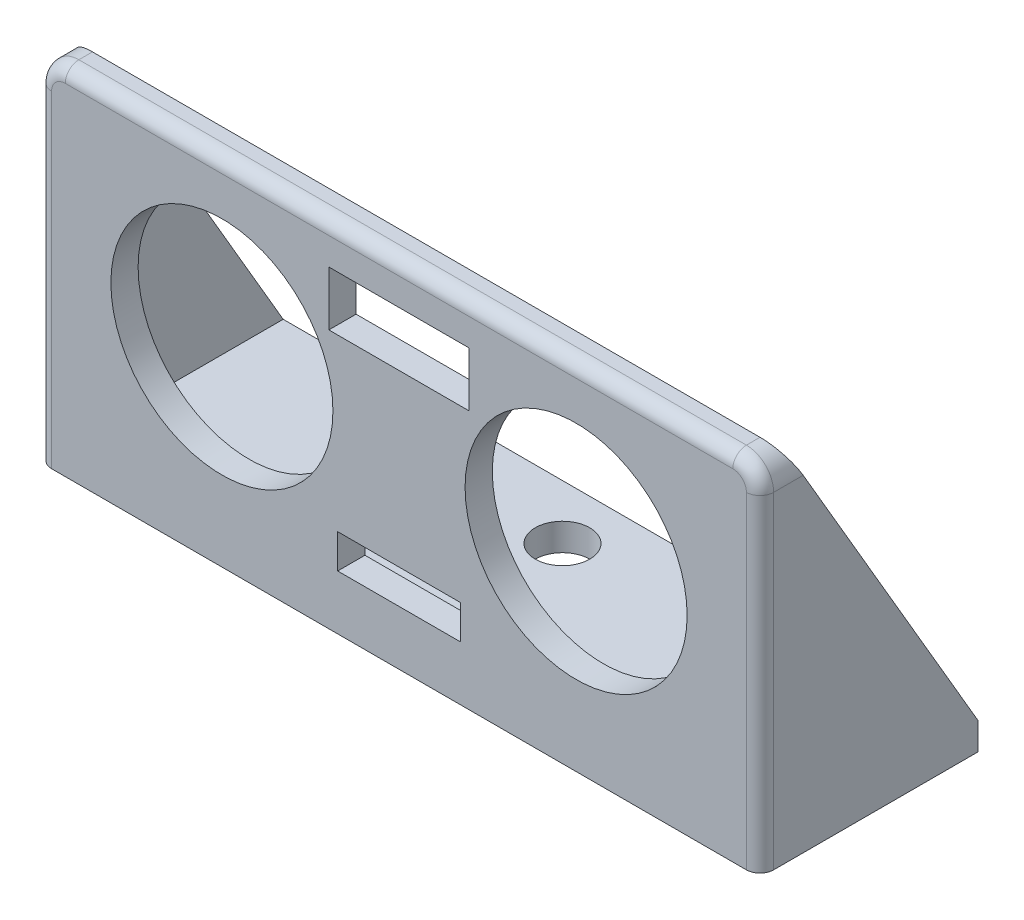
SolidWorks part; units mm, degrees
ref_plane "Alzado" through (0, 0, 0) normal (0, 0, 1) x (1, 0, 0)
ref_plane "Planta" through (0, 0, 0) normal (0, 1, 0) x (1, 0, 0)
ref_plane "Vista lateral" through (0, 0, 0) normal (1, 0, 0) x (0, 0, -1)
sketch "Croquis1" plane through (0, 0, 0) normal (0, 0, 1) x (1, 0, 0)
  line L0 (26.5, 0) -> (26.5, 12) construction
  line L1 (0, 0) -> (53, 0)
  line L2 (0, 0) -> (0, 24)
  line L3 (0, 24) -> (53, 24)
  line L4 (53, 0) -> (53, 24)
  line L6 (21.35, 21) -> (31.65, 21)
  line L7 (21.35, 21) -> (21.35, 17)
  line L8 (21.35, 17) -> (31.65, 17)
  line L9 (31.65, 21) -> (31.65, 17)
  line L10 (22, 4.5) -> (31, 4.5)
  line L11 (22, 4.5) -> (22, 2)
  line L12 (22, 2) -> (31, 2)
  line L13 (31, 4.5) -> (31, 2)
  circle A0 centre (13.5, 12) radius 8.15
  circle A1 centre (39.5, 12) radius 8.15
  point P10 (0, 12)
  dimension "D3" = 16.3
  dimension "D1" = 53
  dimension "D2" = 24
  dimension "D4" = 13.5
  dimension "D5" = 4
  dimension "D6" = 10.3
  dimension "D7" = 9
  dimension "D8" = 2.5
  dimension "D9" = 3
  dimension "D10" = 2
extrude "Saliente-Extruir1" add sketch "Croquis1" along normal blind 2
sketch "Croquis2" plane through (0, 0, 2) normal (0, 0, 1) x (1, 0, 0)
  line L0 (53, 0) -> (53, 24) construction
  line L1 (0, 0) -> (53, 0)
  line L2 (0, 0) -> (0, -2)
  line L3 (0, -2) -> (53, -2)
  line L4 (53, 0) -> (53, -2)
  dimension "D1" = 2
extrude "Saliente-Extruir2" add sketch "Croquis2" against normal blind 16
sketch "Croquis4" plane through (53, 0, 0) normal (1, 0, 0) x (0, 0, -1)
  line L0 (14, -2) -> (14, 0) construction
  line L1 (14, -2) -> (-2, -2) construction
  line L2 (-2, -2) -> (-2, 24) construction
  line L3 (-2, 24) -> (0, 24) construction
  line L4 (14, -2) -> (14, 0)
  line L5 (14, -2) -> (-2, -2)
  line L6 (-2, -2) -> (-2, 24)
  line L7 (-2, 24) -> (0, 24)
  line L8 (0, 24) -> (14, 0)
extrude "Saliente-Extruir3" add sketch "Croquis4" against normal blind 2
extrude "Saliente-Extruir5" add sketch "Croquis4<3>" along normal blind 2 from surface starting at face at (0, 7.3333, -4)
sketch "Croquis4<3>" plane through (53, 0, 0) normal (1, 0, 0) x (0, 0, -1) same geometry as "Croquis4"
sketch "Croquis5" plane through (0, 0, 0) normal (0, 1, 0) x (1, 0, 0)
  line L0 (26.5, 0) -> (26.5, 10) construction
  line L1 (2, 0) -> (51, 0) construction
  line L2 (51, 14) -> (2, 14) construction
  circle A0 centre (12.9, 10) radius 1.65
  circle A1 centre (40.1, 10) radius 1.65
  circle A2 centre (26.5, 10) radius 2
  point P10 (26.5, 5)
  dimension "D1" = 3.3
  dimension "D4" = 4
  dimension "D2" = 4
  dimension "D3" = 13.6
extrude "Cortar-Extruir1" cut sketch "Croquis5" against normal blind 2
fillet "Redondeo1" radius 2 2 edges at (0, 24, 1) (53, 24, 1)
fillet "Redondeo6" radius 1 5 edges at (53, 10, 2) (52.4142, 23.4142, 2) (0, 10, 2) (0.5858, 23.4142, 2) (26.5, 24, 2)
